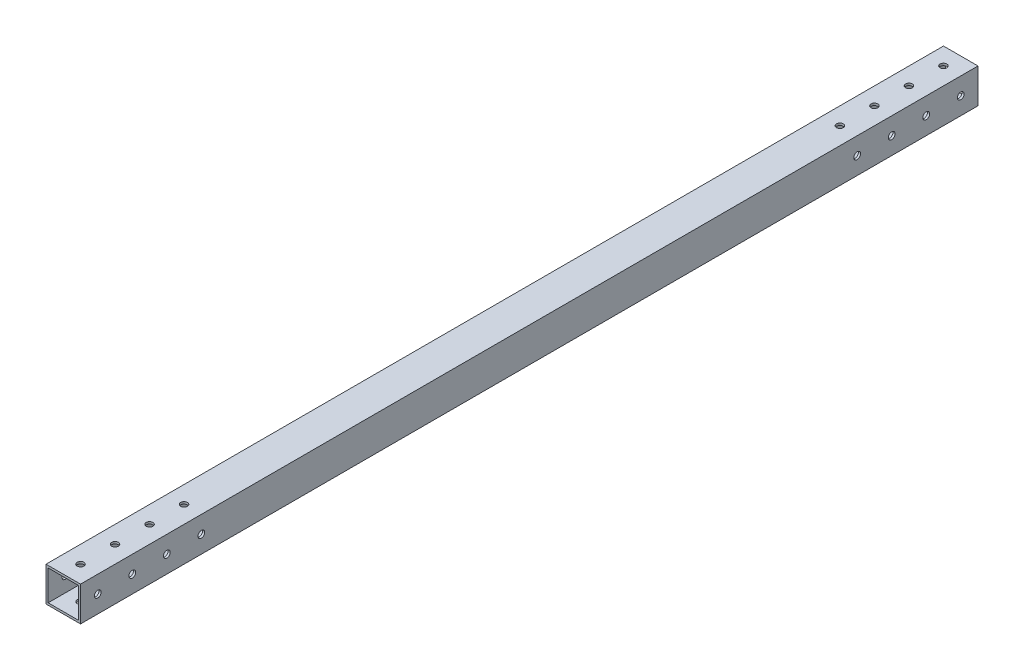
SolidWorks part; units mm, degrees
material "6061-T6 (SS)"
ref_plane "Front Plane" through (0, 0, 0) normal (0, 0, 1) x (1, 0, 0)
ref_plane "Top Plane" through (0, 0, 0) normal (0, 1, 0) x (1, 0, 0)
ref_plane "Right Plane" through (0, 0, 0) normal (1, 0, 0) x (0, 0, -1)
sketch "Sketch5" plane through (0, 0, 0) normal (0, 0, 1) x (1, 0, 0)
  line L1 (0, 0) -> (25.4, 0)
  line L2 (0, 0) -> (0, 25.4)
  line L3 (0, 25.4) -> (25.4, 25.4)
  line L4 (25.4, 0) -> (25.4, 25.4)
  dimension "D1" = 25.4
  dimension "D2" = 25.4
extrude "Boss-Extrude2" add sketch "Sketch5" along normal mid plane 660.4
shell "Shell3" thickness 1.5875 removed face at (12.7, 12.7, 330.2) removed face at (12.7, 12.7, -330.2)
sketch "Sketch6" plane through (0, 25.4, 0) normal (0, 1, 0) x (1, 0, 0)
  line L0 (25.4, 330.2) -> (0, 330.2) construction
  line L1 (0, -330.2) -> (0, 330.2) construction
  circle A0 centre (12.7, 317.5) radius 2.4892
  circle A1 centre (12.7, 292.1) radius 2.4892
  circle A2 centre (12.7, 266.7) radius 2.4892
  circle A3 centre (12.7, 241.3) radius 2.4892
  dimension "D1" = 4.9784
  dimension "D6" = 25.4
  dimension "D7" = 12.7
  dimension "D8" = 4.9784
  dimension "D2" = 25.4
  dimension "D3" = 25.4
  dimension "D4" = 12.7
  dimension "D5" = 12.7
extrude "Cut-Extrude2" cut sketch "Sketch6" against normal through all
sketch "Sketch7" plane through (25.4, 0, 0) normal (1, 0, 0) x (0, 0, -1)
  line L0 (330.2, 0) -> (330.2, 25.4) construction
  line L1 (-330.2, 0) -> (330.2, 0) construction
  line L2 (-330.2, 25.4) -> (330.2, 25.4) construction
  circle A0 centre (292.1, 12.7) radius 2.4892
  circle A1 centre (317.5, 12.7) radius 2.4892
  circle A2 centre (266.7, 12.7) radius 2.4892
  circle A3 centre (241.3, 12.7) radius 2.4892
  dimension "D1" = 4.9784
  dimension "D6" = 25.4
  dimension "D7" = 12.7
  dimension "D8" = 4.9784
  dimension "D2" = 25.4
  dimension "D3" = 25.4
  dimension "D4" = 12.7
  dimension "D5" = 12.7
extrude "Cut-Extrude3" cut sketch "Sketch7" against normal through all
mirror "Mirror2" about plane through (0, 0, 0) normal (0, 0, 1) of "Cut-Extrude3", "Cut-Extrude2"
